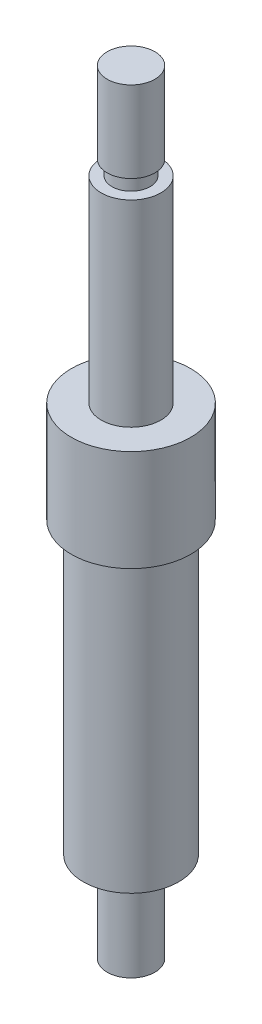
SolidWorks part; units mm, degrees
ref_plane "Front Plane" through (0, 0, 0) normal (0, 0, 1) x (1, 0, 0)
ref_plane "Top Plane" through (0, 0, 0) normal (0, 1, 0) x (1, 0, 0)
ref_plane "Right Plane" through (0, 0, 0) normal (1, 0, 0) x (0, 0, -1)
sketch "Sketch1" plane through (0, 0, 0) normal (0, 0, 1) x (1, 0, 0)
  line L0 (0, 0) -> (0, 67.2246) construction
  line L1 (0, 0) -> (2, 0)
  line L2 (2, 0) -> (2, 7.5612)
  line L3 (2, 7.5612) -> (4, 7.5612)
  line L4 (4, 7.5612) -> (4, 31.8381)
  line L5 (4, 31.8381) -> (5, 31.8381)
  line L7 (5, 40.3337) -> (2.5, 40.3337)
  line L8 (2.5, 40.3337) -> (2.5, 56.8337)
  line L9 (2, 64.8337) -> (0, 64.8337)
  line L10 (2, 64.8337) -> (2, 58.0337)
  line L11 (1.6, 56.8337) -> (2.5, 56.8337)
  line L12 (0, 64.8337) -> (0, 0)
  line L13 (5, 40.3337) -> (5, 31.8381)
  line L15 (2, 58.0337) -> (1.6, 58.0337)
  line L16 (1.6, 58.0337) -> (1.6, 56.8337)
  point P8 (5, 31.8381)
  point P16 (5, 17.7463)
  point P18 (0.9686, 60.9913)
  dimension "D2" = 8
  dimension "D3" = 5
  dimension "D4" = 4
  dimension "D5" = 3.2
  dimension "D6" = 16.5
  dimension "D7" = 10
  dimension "D8" = 1.2
  dimension "D9" = 8
revolve "Revolve1" add sketch "Sketch1" angle 360 about L0
